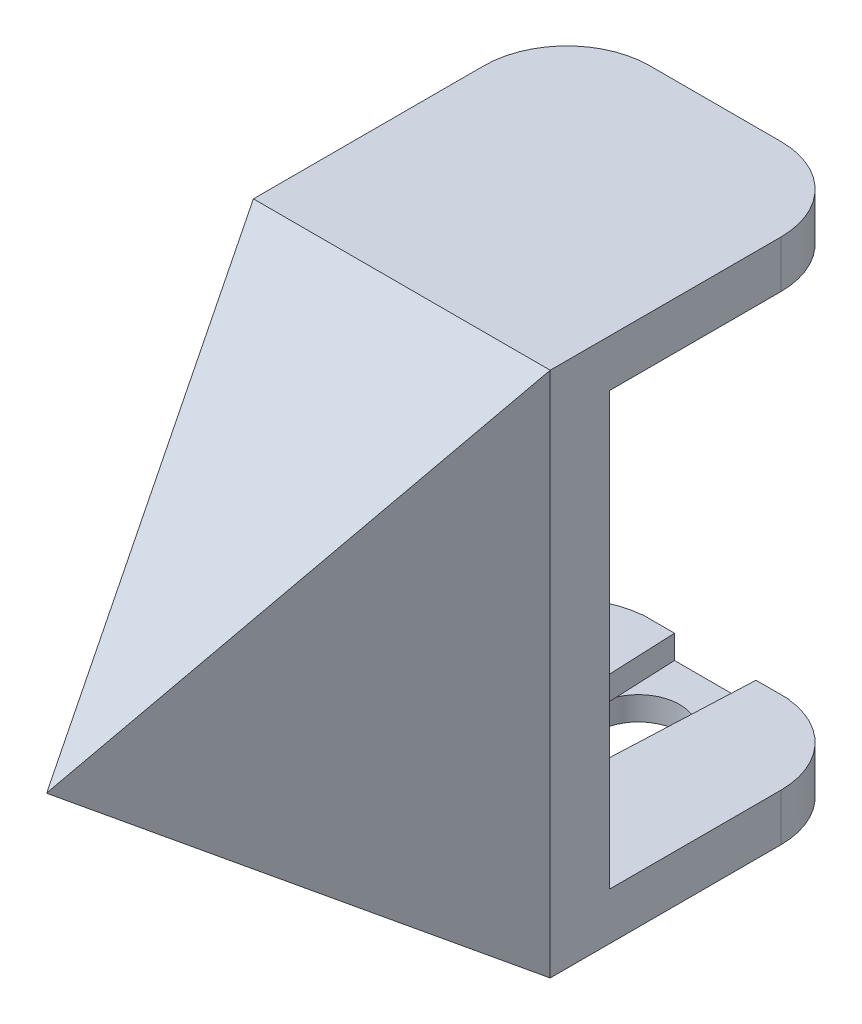
SolidWorks part; units mm, degrees
ref_plane "Front Plane" through (0, 0, 0) normal (0, 0, 1) x (1, 0, 0)
ref_plane "Top Plane" through (0, 0, 0) normal (0, 1, 0) x (1, 0, 0)
ref_plane "Right Plane" through (0, 0, 0) normal (1, 0, 0) x (0, 0, -1)
sketch "Sketch4" plane through (0, 0, 0) normal (0, 0, 1) x (1, 0, 0)
  line L1 (-6.23, -9.975) -> (6.23, -9.975)
  line L2 (-6.23, -9.975) -> (-6.23, 7.275)
  line L3 (-6.23, 7.275) -> (6.23, 7.275)
  line L4 (6.23, -9.975) -> (6.23, 7.275)
  point P4 (0, 7.275)
  dimension "D1" = 12.46
  dimension "D2" = 17.25
  dimension "D3" = 9.975
extrude "Boss-Extrude3" add sketch "Sketch4" along normal blind 6
sketch "Sketch8" plane through (0, -9.975, 0) normal (0, -1, 0) x (-1, 0, 0)
  circle A0 centre (0, -23.55) radius 12.5468
  circle A1 centre (0, -23.55) radius 11.15
  dimension "D1" = 22.3
  dimension "D2" = 23.55
extrude "Boss-Extrude6" add sketch "Sketch8" along normal blind 7.3 and the other way up to surface (17.25 mm away) other way up to face at (0, 7.275, 3)
sketch "Sketch5" plane through (0, 7.275, 0) normal (0, 1, 0) x (1, 0, 0)
  line L8 (12.5468, -23.55) -> (12.5468, 0)
  line L9 (12.5468, 0) -> (6.23, 0)
  line L10 (-12.5468, -23.55) -> (-12.5468, 0)
  line L11 (-12.5468, 0) -> (-6.23, 0)
  line L12 (-6.23, 0) -> (-6.23, -29.7)
  line L14 (6.23, -29.7) -> (6.23, 0)
  line L15 (-6.23, -29.7) -> (6.23, -29.7)
  line L16 (6.23, -6) -> (-6.23, -6) construction
  circle A0 centre (0, -23.55) radius 12.5468 construction
  arc A1 (-12.5468, -23.55) -> (12.5468, -23.55) centre (0, -23.55) ccw
  dimension "D1" = 23.7
  dimension "D2" = 23.55
extrude "Boss-Extrude4" add sketch "Sketch5" against normal up to surface (17.25 mm away) up to face at (0, -9.975, 3)
sketch "Sketch6" plane through (0, 7.275, 0) normal (0, 1, 0) x (1, 0, 0)
  line L0 (6.23, -6) -> (-6.23, -6) construction
  line L3 (6.23, -29.7) -> (-6.23, -29.7) construction
  circle A0 centre (0, -3.5) radius 2
  circle A1 centre (0, -32.2) radius 2
  dimension "D1" = 4
  dimension "D3" = 4
  dimension "D2" = 2.5
  dimension "D4" = 2.5
extrude "Cut-Extrude1" cut sketch "Sketch6" against normal blind 5
chamfer "Chamfer1" distance 0.5 angle 60 2 edges at (0, 7.275, 5.5) (0, 7.275, 34.2) first distance on face at (0, 7.275, 5.5)
sketch "Sketch10" plane through (0, 7.275, 0) normal (0, 1, 0) x (1, 0, 0)
  line L1 (-6.23, -6) -> (6.23, -6)
  line L2 (-6.23, -6) -> (-6.23, -29.7)
  line L3 (-6.23, -29.7) -> (6.23, -29.7)
  line L4 (6.23, -6) -> (6.23, -29.7)
extrude "Cut-Extrude3" cut sketch "Sketch10" against normal up to surface (17.25 mm away) up to face at (0, -9.975, 10.3399)
ref_plane "Plane1" through (0, 0, 36.0968) normal (0, 0, 1) x (1, 0, 0)
sketch "Sketch11" plane through (0, 0, 36.0968) normal (0, 0, 1) x (1, 0, 0)
  line L0 (-11.15, -9.975) -> (11.15, -9.975) construction
  line L1 (-2.5, -6.975) -> (2.5, -6.975)
  line L2 (-2.5, -6.975) -> (-2.5, -9.975)
  line L3 (-2.5, -9.975) -> (2.5, -9.975)
  line L4 (2.5, -6.975) -> (2.5, -9.975)
  point P4 (0, -6.975)
  dimension "D1" = 0
  dimension "D2" = 5
  dimension "D3" = 3
extrude "Cut-Extrude4" cut sketch "Sketch11" against normal up to next
sketch "Sketch13" plane through (0, -17.275, 0) normal (0, -1, 0) x (1, 0, 0)
  line L0 (-12.5468, 23.55) -> (-12.5468, 0)
  line L1 (-12.5468, 0) -> (12.5468, 0)
  line L2 (12.5468, 0) -> (12.5468, 23.55)
  arc A0 (-12.5468, 23.55) -> (12.5468, 23.55) centre (0, 23.55) ccw
  point P3 (0, 0)
extrude "Boss-Extrude7" add sketch "Sketch13" against normal up to surface (7.3 mm away) up to face at (0, -9.975, 10.3399)
sketch "Sketch15" plane through (0, 7.275, 0) normal (0, 1, 0) x (1, 0, 0)
  line L0 (-12.5468, 0) -> (12.5468, 0)
  line L1 (12.5468, 0) -> (12.5468, -23.55)
  line L2 (-12.5468, 0) -> (-12.5468, -23.55)
  line L3 (6.23, -6) -> (6.23, -29.7) construction
  line L4 (-6.23, -0.8) -> (6.23, -0.8)
  line L5 (-6.23, -0.8) -> (-6.23, -33.5)
  line L6 (-5.23, -34.5) -> (5.23, -34.5)
  line L7 (6.23, -0.8) -> (6.23, -33.5)
  arc A0 (-12.5468, -23.55) -> (12.5468, -23.55) centre (0, -23.55) ccw
  circle A1 centre (0, -3.5) radius 2 construction
  arc A2 (5.23, -34.5) -> (6.23, -33.5) centre (5.23, -33.5) ccw
  arc A3 (-6.23, -33.5) -> (-5.23, -34.5) centre (-5.23, -33.5) ccw
  point P15 (0, -0.8)
  dimension "D1" = 0.8
  dimension "D3" = 1
  dimension "D2" = 2.7
  dimension "D4" = 0
  dimension "D5" = 34.5
extrude "Boss-Extrude9" add sketch "Sketch15" along normal blind 10
sketch "Sketch17" plane through (-12.5468, 4.7282, 0) normal (1, 0, 0) x (0, -1, 0)
  line L0 (26.9782, 26.5) -> (26.9782, 0)
  line L1 (26.9782, 0) -> (-17.5218, 0)
  line L2 (-17.5218, 0) -> (-17.5218, 26.5)
  line L3 (-17.5218, 26.5) -> (-13.5218, 26.5)
  line L4 (-13.5218, 26.5) -> (-13.5218, 5)
  line L5 (-13.5218, 5) -> (22.9782, 5)
  line L6 (22.9782, 5) -> (22.9782, 26.5)
  line L7 (22.9782, 26.5) -> (26.9782, 26.5)
  point P2 (4.7282, 5)
  point P10 (4.7282, 0)
  dimension "D1" = 4
  dimension "D2" = 36.5
  dimension "D3" = 0
  dimension "D4" = 26.5
  dimension "D5" = 5
extrude "Boss-Extrude10" add sketch "Sketch17" along normal up to surface (25.0936 mm away) up to face at (12.5468, 0, 11.775)
sketch "Sketch18" plane through (0, -18.25, 0) normal (0, 1, 0) x (0, 0, 1)
  line L0 (-26.5, -12.5468) -> (-26.5, 12.5468) construction
  line L1 (-26.5, 6.2191) -> (-5, 6.2191)
  line L2 (-26.5, 6.2191) -> (-26.5, -6.2191)
  line L3 (-26.5, -6.2191) -> (-5, -6.2191)
  line L4 (-5, 6.2191) -> (-5, -6.2191)
  line L5 (-5, -12.5468) -> (-5, 12.5468) construction
  point P6 (-26.5, 0)
  point P7 (-26.5, 0)
  dimension "D1" = 0
extrude "Cut-Extrude5" cut sketch "Sketch18" against normal blind 2
sketch "Sketch19" plane through (0, -20.25, 0) normal (0, 1, 0) x (0, 0, 1)
  line L0 (-26.5, -12.5468) -> (-26.5, 12.5468) construction
  line L1 (-26.5, 12.5468) -> (-26.5, -12.5468) construction
  circle A0 centre (-20, 0) radius 3.5
  point P7 (-26.5, 0)
  dimension "D1" = 7
  dimension "D2" = 6.5
extrude "Cut-Extrude6" cut sketch "Sketch19" against normal through all both and the other way through all
fillet "Fillet1" radius 7 4 edges at (12.5468, -20.25, -26.5) (-12.5468, -20.25, -26.5) (-12.5468, 20.25, -26.5) (12.5468, 20.25, -26.5)
ref_plane "Plane2" through (0, 0, 0) normal (1, 0, 0) x (0, 0, -1)
ref_plane "Plane3" through (0, 0, 0) normal (0, -1, 0) x (-1, 0, 0)
sketch "Sketch20" plane through (0, 17.275, 0) normal (0, 1, 0) x (1, 0, 0)
  line L1 (12.5468, 0) -> (-12.5468, 0)
  line L2 (12.5468, 0) -> (12.5468, -36.0968)
  line L3 (12.5468, -36.0968) -> (-12.5468, -36.0968)
  line L4 (-12.5468, 0) -> (-12.5468, -36.0968)
extrude "Cut-Extrude7" cut sketch "Sketch20" against normal through all both and the other way through all
sketch "Sketch21" plane through (0, 22.25, 0) normal (0, 1, 0) x (1, 0, 0)
  line L0 (12.5468, 0) -> (-0.0254, -30)
  line L1 (-0.0254, -30) -> (-12.5468, 0)
  line L2 (-12.5468, 0) -> (12.5468, 0)
  dimension "D1" = 30
extrude "Boss-Extrude11" add sketch "Sketch21" against normal up to vertex (44.5 mm away) up to point (-12.5468, -22.25, 0)
sketch "Sketch22" plane through (0, 0, 0) normal (1, 0, 0) x (0, 0, -1)
  line L13 (0, 22.25) -> (-30, 0.01)
  line L14 (-30, -22.25) -> (-30, 22.25) construction
  line L15 (-30, 0.01) -> (-30, 22.25)
  line L16 (-30, 22.25) -> (0, 22.25)
  line L17 (0, -22.25) -> (-30, -22.25)
  line L18 (-30, -22.25) -> (-30, -0.01)
  line L19 (-30, -0.01) -> (0, -22.25)
  dimension "D1" = 0.02
  dimension "D2" = 0.01
extrude "Cut-Extrude8" cut sketch "Sketch22" against normal through all both and the other way through all
sketch "Sketch23" plane through (0, 0, 0) normal (0, 0, -1) x (-1, 0, 0)
  line L0 (12.5468, 18.25) -> (0, 0)
  line L1 (0, 0) -> (12.5468, -22.25)
  line L2 (12.5468, -22.25) -> (12.5468, 18.25)
extrude "Cut-Extrude9" cut sketch "Sketch23" against normal through all both and the other way through all
sketch "Sketch24" plane through (0, 22.25, 0) normal (0, 1, 0) x (1, 0, 0)
  circle A0 centre (0, 20) radius 6.5
  dimension "D1" = 13
extrude "Boss-Extrude12" add sketch "Sketch24" against normal blind 5
sketch "Sketch25" plane through (0, 17.25, 0) normal (0, -1, 0) x (1, 0, 0)
  circle A0 centre (0, -20) radius 6.075
  dimension "D1" = 12.15
extrude "Boss-Extrude13" add sketch "Sketch25" along normal blind 5
fillet "Fillet2" radius 1 1 edges at (0, 12.25, -26.075)
sketch "Sketch26" plane through (0, -20.25, 0) normal (0, 1, 0) x (1, 0, 0)
  line L0 (-6.2191, 5) -> (-2.5, 5)
  line L1 (12.5468, 5) -> (-12.5468, 5) construction
  line L2 (-2.5, 5) -> (-3.1585, 20)
  line L4 (3.1585, 20) -> (3.4438, 26.5)
  line L5 (-6.2191, 26.5) -> (-6.2191, 5)
  line L6 (2.5, 5) -> (6.2191, 5)
  line L7 (6.2191, 5) -> (6.2191, 26.5)
  line L8 (3.4438, 26.5) -> (6.2191, 26.5)
  line L10 (3.1585, 20) -> (2.5, 5)
  line L11 (0, -10.725) -> (0, 10.725) construction
  line L13 (-3.1585, 20) -> (-3.4439, 26.5)
  line L14 (-3.4439, 26.5) -> (-6.2191, 26.5)
  line L15 (6.2191, 5) -> (6.2191, 26.4676) construction
  line L16 (5.5468, 26.5) -> (-5.5468, 26.5) construction
  circle A0 centre (0, 20) radius 3.5 construction
  point P8 (6.2191, 8.7424)
  point P19 (-3.7766, 9.9957)
  point P20 (2.5, 7.4123)
  point P21 (3.7432, 10.1492)
  dimension "D1" = 5
  dimension "D2" = 2.5
  dimension "D3" = 0
  dimension "D4" = 0
  dimension "D5" = 6.317
  dimension "D6" = 3.1585
extrude "Boss-Extrude14" add sketch "Sketch26" along normal up to surface (2 mm away) up to face at (-8.2924, -18.25, -15.3619)
sketch "Sketch27" plane through (0, -22.25, 0) normal (0, -1, 0) x (1, 0, 0)
  circle A0 centre (0, -10) radius 0.75
  circle A1 centre (0, -20) radius 3.5 construction
  dimension "D1" = 1.5
  dimension "D2" = 10
  dimension "D3" = 0
extrude "Cut-Extrude10" cut sketch "Sketch27" against normal up to next
